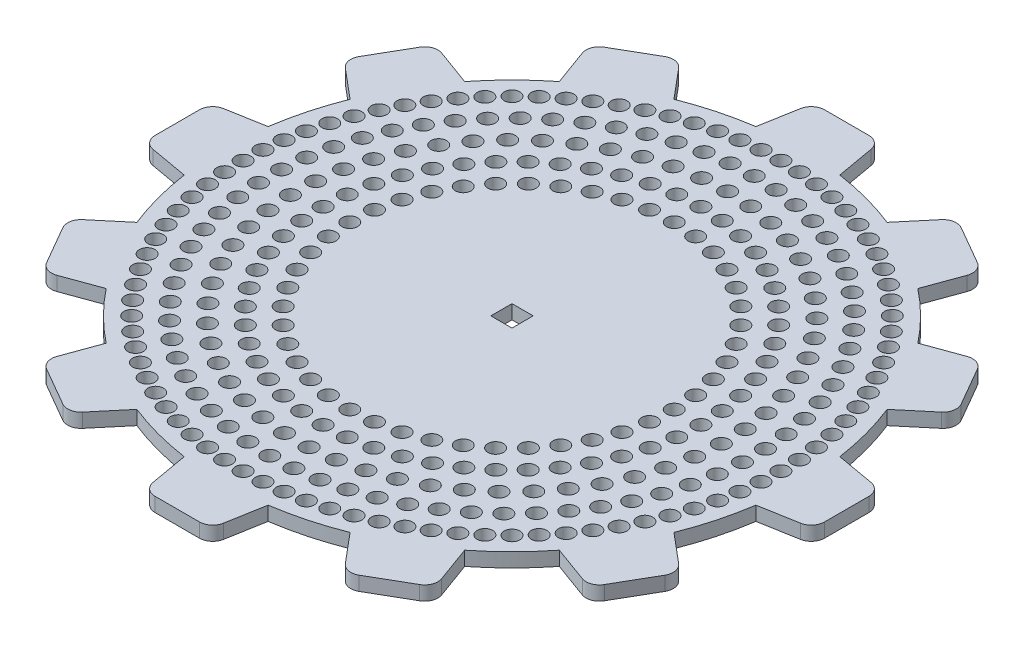
SolidWorks part; units mm, degrees
material "Balsa"
ref_plane "Front Plane" through (0, 0, 0) normal (0, 0, 1) x (1, 0, 0)
ref_plane "Top Plane" through (0, 0, 0) normal (0, 1, 0) x (1, 0, 0)
ref_plane "Right Plane" through (0, 0, 0) normal (1, 0, 0) x (0, 0, -1)
sketch "Sketch1" plane through (0, 0, 0) normal (0, 1, 0) x (1, 0, 0)
  line L0 (0, 109) -> (0, 121) construction
  line L1 (-4.7625, 4.7625) -> (4.7625, 4.7625)
  line L2 (-4.7625, 4.7625) -> (-4.7625, -4.7625)
  line L7 (-4.7625, -4.7625) -> (4.7625, -4.7625)
  line L8 (0, 109) -> (0, 97) construction
  line L9 (0, 97) -> (0, 85) construction
  line L10 (0, 85) -> (0, 73) construction
  line L11 (4.7625, 4.7625) -> (4.7625, -4.7625)
  line L12 (-4.7625, 4.7625) -> (4.7625, -4.7625) construction
  line L13 (-4.7625, -4.7625) -> (4.7625, 4.7625) construction
  circle A0 centre (0, 0) radius 130
  circle A39 centre (0, 73) radius 3.5
  circle A40 centre (0, 85) radius 3.5
  circle A41 centre (0, 97) radius 3.5
  circle A42 centre (0, 109) radius 3.5
  circle A43 centre (10.3611, 108.5064) radius 3.5
  circle A44 centre (20.6284, 107.0302) radius 3.5
  circle A45 centre (30.7088, 104.5847) radius 3.5
  circle A46 centre (40.5112, 101.1921) radius 3.5
  circle A47 centre (49.9467, 96.8831) radius 3.5
  circle A48 centre (58.9298, 91.6966) radius 3.5
  circle A49 centre (67.3793, 85.6798) radius 3.5
  circle A50 centre (75.2186, 78.887) radius 3.5
  circle A51 centre (82.3767, 71.3798) radius 3.5
  circle A52 centre (88.7888, 63.2262) radius 3.5
  circle A53 centre (94.3968, 54.5) radius 3.5
  circle A54 centre (99.1499, 45.2802) radius 3.5
  circle A55 centre (103.0051, 35.6504) radius 3.5
  circle A56 centre (105.9275, 25.6977) radius 3.5
  circle A57 centre (107.8905, 15.5123) radius 3.5
  circle A58 centre (108.8765, 5.1864) radius 3.5
  circle A59 centre (108.8765, -5.1864) radius 3.5
  circle A60 centre (107.8905, -15.5123) radius 3.5
  circle A61 centre (105.9275, -25.6977) radius 3.5
  circle A62 centre (103.0051, -35.6504) radius 3.5
  circle A63 centre (99.1499, -45.2802) radius 3.5
  circle A64 centre (94.3968, -54.5) radius 3.5
  circle A65 centre (88.7888, -63.2262) radius 3.5
  circle A66 centre (82.3767, -71.3798) radius 3.5
  circle A67 centre (75.2186, -78.887) radius 3.5
  circle A68 centre (67.3793, -85.6798) radius 3.5
  circle A69 centre (58.9298, -91.6966) radius 3.5
  circle A70 centre (49.9467, -96.8831) radius 3.5
  circle A71 centre (40.5112, -101.1921) radius 3.5
  circle A72 centre (30.7088, -104.5847) radius 3.5
  circle A73 centre (20.6284, -107.0302) radius 3.5
  circle A74 centre (10.3611, -108.5064) radius 3.5
  circle A75 centre (0, -109) radius 3.5
  circle A76 centre (-10.3611, -108.5064) radius 3.5
  circle A77 centre (-20.6284, -107.0302) radius 3.5
  circle A78 centre (-30.7088, -104.5847) radius 3.5
  circle A79 centre (-40.5112, -101.1921) radius 3.5
  circle A80 centre (-49.9467, -96.8831) radius 3.5
  circle A81 centre (-58.9298, -91.6966) radius 3.5
  circle A82 centre (-67.3793, -85.6798) radius 3.5
  circle A83 centre (-75.2186, -78.887) radius 3.5
  circle A84 centre (-82.3767, -71.3798) radius 3.5
  circle A85 centre (-88.7888, -63.2262) radius 3.5
  circle A86 centre (-94.3968, -54.5) radius 3.5
  circle A87 centre (-99.1499, -45.2802) radius 3.5
  circle A88 centre (-103.0051, -35.6504) radius 3.5
  circle A89 centre (-105.9275, -25.6977) radius 3.5
  circle A90 centre (-107.8905, -15.5123) radius 3.5
  circle A91 centre (-108.8765, -5.1864) radius 3.5
  circle A92 centre (-108.8765, 5.1864) radius 3.5
  circle A93 centre (-107.8905, 15.5123) radius 3.5
  circle A94 centre (-105.9275, 25.6977) radius 3.5
  circle A95 centre (-103.0051, 35.6504) radius 3.5
  circle A96 centre (-99.1499, 45.2802) radius 3.5
  circle A97 centre (-94.3968, 54.5) radius 3.5
  circle A98 centre (-88.7888, 63.2262) radius 3.5
  circle A99 centre (-82.3767, 71.3798) radius 3.5
  circle A100 centre (-75.2186, 78.887) radius 3.5
  circle A101 centre (-67.3793, 85.6798) radius 3.5
  circle A102 centre (-58.9298, 91.6966) radius 3.5
  circle A103 centre (-49.9467, 96.8831) radius 3.5
  circle A104 centre (-40.5112, 101.1921) radius 3.5
  circle A105 centre (-30.7088, 104.5847) radius 3.5
  circle A106 centre (-20.6284, 107.0302) radius 3.5
  circle A107 centre (-10.3611, 108.5064) radius 3.5
  circle A108 centre (11.0572, 96.3677) radius 3.5
  circle A109 centre (21.9702, 94.4792) radius 3.5
  circle A110 centre (32.5968, 91.3589) radius 3.5
  circle A111 centre (42.7984, 87.0476) radius 3.5
  circle A112 centre (52.4422, 81.6016) radius 3.5
  circle A113 centre (61.4022, 75.0917) radius 3.5
  circle A114 centre (69.5618, 67.6029) radius 3.5
  circle A115 centre (76.8145, 59.2328) radius 3.5
  circle A116 centre (83.0659, 50.0906) radius 3.5
  circle A117 centre (88.2343, 40.2953) radius 3.5
  circle A118 centre (92.2525, 29.9746) radius 3.5
  circle A119 centre (95.068, 19.2633) radius 3.5
  circle A120 centre (96.6442, 8.3008) radius 3.5
  circle A121 centre (96.9604, -2.7699) radius 3.5
  circle A122 centre (96.0127, -13.8045) radius 3.5
  circle A123 centre (93.8132, -24.6592) radius 3.5
  circle A124 centre (90.3908, -35.1923) radius 3.5
  circle A125 centre (85.79, -45.2667) radius 3.5
  circle A126 centre (80.0708, -54.751) radius 3.5
  circle A127 centre (73.3077, -63.5215) radius 3.5
  circle A128 centre (65.589, -71.4639) radius 3.5
  circle A129 centre (57.0152, -78.4746) radius 3.5
  circle A130 centre (47.6981, -84.4624) radius 3.5
  circle A131 centre (37.7592, -89.349) radius 3.5
  circle A132 centre (27.3281, -93.0708) radius 3.5
  circle A133 centre (16.5407, -95.5793) radius 3.5
  circle A134 centre (5.5376, -96.8418) radius 3.5
  circle A135 centre (-5.5376, -96.8418) radius 3.5
  circle A136 centre (-16.5407, -95.5793) radius 3.5
  circle A137 centre (-27.3281, -93.0708) radius 3.5
  circle A138 centre (-37.7592, -89.349) radius 3.5
  circle A139 centre (-47.6981, -84.4624) radius 3.5
  circle A140 centre (-57.0152, -78.4746) radius 3.5
  circle A141 centre (-65.589, -71.4639) radius 3.5
  circle A142 centre (-73.3077, -63.5215) radius 3.5
  circle A143 centre (-80.0708, -54.751) radius 3.5
  circle A144 centre (-85.79, -45.2667) radius 3.5
  circle A145 centre (-90.3908, -35.1923) radius 3.5
  circle A146 centre (-93.8132, -24.6592) radius 3.5
  circle A147 centre (-96.0127, -13.8045) radius 3.5
  circle A148 centre (-96.9604, -2.7699) radius 3.5
  circle A149 centre (-96.6442, 8.3008) radius 3.5
  circle A150 centre (-95.068, 19.2633) radius 3.5
  circle A151 centre (-92.2525, 29.9746) radius 3.5
  circle A152 centre (-88.2343, 40.2953) radius 3.5
  circle A153 centre (-83.0659, 50.0906) radius 3.5
  circle A154 centre (-76.8145, 59.2328) radius 3.5
  circle A155 centre (-69.5618, 67.6029) radius 3.5
  circle A156 centre (-61.4022, 75.0917) radius 3.5
  circle A157 centre (-52.4422, 81.6016) radius 3.5
  circle A158 centre (-42.7984, 87.0476) radius 3.5
  circle A159 centre (-32.5968, 91.3589) radius 3.5
  circle A160 centre (-21.9702, 94.4792) radius 3.5
  circle A161 centre (-11.0572, 96.3677) radius 3.5
  circle A162 centre (10.2456, 84.3803) radius 3.5
  circle A163 centre (20.3418, 82.5301) radius 3.5
  circle A164 centre (30.1414, 79.4764) radius 3.5
  circle A165 centre (39.5015, 75.2638) radius 3.5
  circle A166 centre (48.2855, 69.9536) radius 3.5
  circle A167 centre (56.3654, 63.6234) radius 3.5
  circle A168 centre (63.6234, 56.3654) radius 3.5
  circle A169 centre (69.9536, 48.2855) radius 3.5
  circle A170 centre (75.2638, 39.5015) radius 3.5
  circle A171 centre (79.4764, 30.1414) radius 3.5
  circle A172 centre (82.5301, 20.3418) radius 3.5
  circle A173 centre (84.3803, 10.2456) radius 3.5
  circle A174 centre (85, 0) radius 3.5
  circle A175 centre (84.3803, -10.2456) radius 3.5
  circle A176 centre (82.5301, -20.3418) radius 3.5
  circle A177 centre (79.4764, -30.1414) radius 3.5
  circle A178 centre (75.2638, -39.5015) radius 3.5
  circle A179 centre (69.9536, -48.2855) radius 3.5
  circle A180 centre (63.6234, -56.3654) radius 3.5
  circle A181 centre (56.3654, -63.6234) radius 3.5
  circle A182 centre (48.2855, -69.9536) radius 3.5
  circle A183 centre (39.5015, -75.2638) radius 3.5
  circle A184 centre (30.1414, -79.4764) radius 3.5
  circle A185 centre (20.3418, -82.5301) radius 3.5
  circle A186 centre (10.2456, -84.3803) radius 3.5
  circle A187 centre (0, -85) radius 3.5
  circle A188 centre (-10.2456, -84.3803) radius 3.5
  circle A189 centre (-20.3418, -82.5301) radius 3.5
  circle A190 centre (-30.1414, -79.4764) radius 3.5
  circle A191 centre (-39.5015, -75.2638) radius 3.5
  circle A192 centre (-48.2855, -69.9536) radius 3.5
  circle A193 centre (-56.3654, -63.6234) radius 3.5
  circle A194 centre (-63.6234, -56.3654) radius 3.5
  circle A195 centre (-69.9536, -48.2855) radius 3.5
  circle A196 centre (-75.2638, -39.5015) radius 3.5
  circle A197 centre (-79.4764, -30.1414) radius 3.5
  circle A198 centre (-82.5301, -20.3418) radius 3.5
  circle A199 centre (-84.3803, -10.2456) radius 3.5
  circle A200 centre (-85, 0) radius 3.5
  circle A201 centre (-84.3803, 10.2456) radius 3.5
  circle A202 centre (-82.5301, 20.3418) radius 3.5
  circle A203 centre (-79.4764, 30.1414) radius 3.5
  circle A204 centre (-75.2638, 39.5015) radius 3.5
  circle A205 centre (-69.9536, 48.2855) radius 3.5
  circle A206 centre (-63.6234, 56.3654) radius 3.5
  circle A207 centre (-56.3654, 63.6234) radius 3.5
  circle A208 centre (-48.2855, 69.9536) radius 3.5
  circle A209 centre (-39.5015, 75.2638) radius 3.5
  circle A210 centre (-30.1414, 79.4764) radius 3.5
  circle A211 centre (-20.3418, 82.5301) radius 3.5
  circle A212 centre (-10.2456, 84.3803) radius 3.5
  circle A214 centre (10.389, 72.257) radius 3.5
  circle A215 centre (20.5665, 70.043) radius 3.5
  circle A216 centre (30.3253, 66.4031) radius 3.5
  circle A217 centre (39.4668, 61.4115) radius 3.5
  circle A218 centre (47.8048, 55.1697) radius 3.5
  circle A219 centre (55.1697, 47.8048) radius 3.5
  circle A220 centre (61.4115, 39.4668) radius 3.5
  circle A221 centre (66.4031, 30.3253) radius 3.5
  circle A222 centre (70.043, 20.5665) radius 3.5
  circle A223 centre (72.257, 10.389) radius 3.5
  circle A224 centre (73, 0) radius 3.5
  circle A225 centre (72.257, -10.389) radius 3.5
  circle A226 centre (70.043, -20.5665) radius 3.5
  circle A227 centre (66.4031, -30.3253) radius 3.5
  circle A228 centre (61.4115, -39.4668) radius 3.5
  circle A229 centre (55.1697, -47.8048) radius 3.5
  circle A230 centre (47.8048, -55.1697) radius 3.5
  circle A231 centre (39.4668, -61.4115) radius 3.5
  circle A232 centre (30.3253, -66.4031) radius 3.5
  circle A233 centre (20.5665, -70.043) radius 3.5
  circle A234 centre (10.389, -72.257) radius 3.5
  circle A235 centre (0, -73) radius 3.5
  circle A236 centre (-10.389, -72.257) radius 3.5
  circle A237 centre (-20.5665, -70.043) radius 3.5
  circle A238 centre (-30.3253, -66.4031) radius 3.5
  circle A239 centre (-39.4668, -61.4115) radius 3.5
  circle A240 centre (-47.8048, -55.1697) radius 3.5
  circle A241 centre (-55.1697, -47.8048) radius 3.5
  circle A242 centre (-61.4115, -39.4668) radius 3.5
  circle A243 centre (-66.4031, -30.3253) radius 3.5
  circle A244 centre (-70.043, -20.5665) radius 3.5
  circle A245 centre (-72.257, -10.389) radius 3.5
  circle A246 centre (-73, 0) radius 3.5
  circle A247 centre (-72.257, 10.389) radius 3.5
  circle A248 centre (-70.043, 20.5665) radius 3.5
  circle A249 centre (-66.4031, 30.3253) radius 3.5
  circle A250 centre (-61.4115, 39.4668) radius 3.5
  circle A251 centre (-55.1697, 47.8048) radius 3.5
  circle A252 centre (-47.8048, 55.1697) radius 3.5
  circle A253 centre (-39.4668, 61.4115) radius 3.5
  circle A254 centre (-30.3253, 66.4031) radius 3.5
  circle A255 centre (-20.5665, 70.043) radius 3.5
  circle A256 centre (-10.389, 72.257) radius 3.5
  circle A258 centre (0, 121) radius 3.5
  circle A259 centre (8.632, 120.6917) radius 3.5
  circle A260 centre (17.2201, 119.7684) radius 3.5
  circle A261 centre (25.7204, 118.2348) radius 3.5
  circle A262 centre (34.0896, 116.0986) radius 3.5
  circle A263 centre (42.2852, 113.3709) radius 3.5
  circle A264 centre (50.2652, 110.0655) radius 3.5
  circle A265 centre (57.9891, 106.1992) radius 3.5
  circle A266 centre (65.4175, 101.7917) radius 3.5
  circle A267 centre (72.5126, 96.8655) radius 3.5
  circle A268 centre (79.2381, 91.4457) radius 3.5
  circle A269 centre (85.5599, 85.5599) radius 3.5
  circle A270 centre (91.4457, 79.2381) radius 3.5
  circle A271 centre (96.8655, 72.5126) radius 3.5
  circle A272 centre (101.7917, 65.4175) radius 3.5
  circle A273 centre (106.1992, 57.9891) radius 3.5
  circle A274 centre (110.0655, 50.2652) radius 3.5
  circle A275 centre (113.3709, 42.2852) radius 3.5
  circle A276 centre (116.0986, 34.0896) radius 3.5
  circle A277 centre (118.2348, 25.7204) radius 3.5
  circle A278 centre (119.7684, 17.2201) radius 3.5
  circle A279 centre (120.6917, 8.632) radius 3.5
  circle A280 centre (121, 0) radius 3.5
  circle A281 centre (120.6917, -8.632) radius 3.5
  circle A282 centre (119.7684, -17.2201) radius 3.5
  circle A283 centre (118.2348, -25.7204) radius 3.5
  circle A284 centre (116.0986, -34.0896) radius 3.5
  circle A285 centre (113.3709, -42.2852) radius 3.5
  circle A286 centre (110.0655, -50.2652) radius 3.5
  circle A287 centre (106.1992, -57.9891) radius 3.5
  circle A288 centre (101.7917, -65.4175) radius 3.5
  circle A289 centre (96.8655, -72.5126) radius 3.5
  circle A290 centre (91.4457, -79.2381) radius 3.5
  circle A291 centre (85.5599, -85.5599) radius 3.5
  circle A292 centre (79.2381, -91.4457) radius 3.5
  circle A293 centre (72.5126, -96.8655) radius 3.5
  circle A294 centre (65.4175, -101.7917) radius 3.5
  circle A295 centre (57.9891, -106.1992) radius 3.5
  circle A296 centre (50.2652, -110.0655) radius 3.5
  circle A297 centre (42.2852, -113.3709) radius 3.5
  circle A298 centre (34.0896, -116.0986) radius 3.5
  circle A299 centre (25.7204, -118.2348) radius 3.5
  circle A300 centre (17.2201, -119.7684) radius 3.5
  circle A301 centre (8.632, -120.6917) radius 3.5
  circle A302 centre (0, -121) radius 3.5
  circle A303 centre (-8.632, -120.6917) radius 3.5
  circle A304 centre (-17.2201, -119.7684) radius 3.5
  circle A305 centre (-25.7204, -118.2348) radius 3.5
  circle A306 centre (-34.0896, -116.0986) radius 3.5
  circle A307 centre (-42.2852, -113.3709) radius 3.5
  circle A308 centre (-50.2652, -110.0655) radius 3.5
  circle A309 centre (-57.9891, -106.1992) radius 3.5
  circle A310 centre (-65.4175, -101.7917) radius 3.5
  circle A311 centre (-72.5126, -96.8655) radius 3.5
  circle A312 centre (-79.2381, -91.4457) radius 3.5
  circle A313 centre (-85.5599, -85.5599) radius 3.5
  circle A314 centre (-91.4457, -79.2381) radius 3.5
  circle A315 centre (-96.8655, -72.5126) radius 3.5
  circle A316 centre (-101.7917, -65.4175) radius 3.5
  circle A317 centre (-106.1992, -57.9891) radius 3.5
  circle A318 centre (-110.0655, -50.2652) radius 3.5
  circle A319 centre (-113.3709, -42.2852) radius 3.5
  circle A320 centre (-116.0986, -34.0896) radius 3.5
  circle A321 centre (-118.2348, -25.7204) radius 3.5
  circle A322 centre (-119.7684, -17.2201) radius 3.5
  circle A323 centre (-120.6917, -8.632) radius 3.5
  circle A324 centre (-121, 0) radius 3.5
  circle A325 centre (-120.6917, 8.632) radius 3.5
  circle A326 centre (-119.7684, 17.2201) radius 3.5
  circle A327 centre (-118.2348, 25.7204) radius 3.5
  circle A328 centre (-116.0986, 34.0896) radius 3.5
  circle A329 centre (-113.3709, 42.2852) radius 3.5
  circle A330 centre (-110.0655, 50.2652) radius 3.5
  circle A331 centre (-106.1992, 57.9891) radius 3.5
  circle A332 centre (-101.7917, 65.4175) radius 3.5
  circle A333 centre (-96.8655, 72.5126) radius 3.5
  circle A334 centre (-91.4457, 79.2381) radius 3.5
  circle A335 centre (-85.5599, 85.5599) radius 3.5
  circle A336 centre (-79.2381, 91.4457) radius 3.5
  circle A337 centre (-72.5126, 96.8655) radius 3.5
  circle A338 centre (-65.4175, 101.7917) radius 3.5
  circle A339 centre (-57.9891, 106.1992) radius 3.5
  circle A340 centre (-50.2652, 110.0655) radius 3.5
  circle A341 centre (-42.2852, 113.3709) radius 3.5
  circle A342 centre (-34.0896, 116.0986) radius 3.5
  circle A343 centre (-25.7204, 118.2348) radius 3.5
  circle A344 centre (-17.2201, 119.7684) radius 3.5
  circle A345 centre (-8.632, 120.6917) radius 3.5
  point P619 (0, 0)
  dimension "D2" = 12
  dimension "D3" = 260
  dimension "D4" = 73
  dimension "D12" = 7
  dimension "D5" = 9.525
  dimension "D8" = 66
  dimension "D9" = 55
  dimension "D10" = 52
  dimension "D11" = 44
  dimension "D6" = 88
extrude "Boss-Extrude1" add sketch "Sketch1" along normal blind 6.35
sketch "Sketch2" plane through (0, 6.35, 0) normal (0, 1, 0) x (1, 0, 0)
  line L0 (0, 0) -> (0, 202.4314) construction
  line L1 (0, 0) -> (-221.3243, 0) construction
  line L2 (0, 0) -> (223.2936, 0) construction
  line L3 (0, 150.6218) -> (15, 150.6218)
  line L4 (0, 150.6218) -> (-15, 150.6218)
  line L5 (-15, 150.6218) -> (-18.8792, 128.6218)
  line L6 (15, 150.6218) -> (18.8792, 128.6218)
  line L7 (62.3205, 137.9423) -> (47.9611, 120.8294)
  line L8 (75.3109, 130.4423) -> (88.3013, 122.9423)
  line L9 (75.3109, 130.4423) -> (62.3205, 137.9423)
  line L10 (88.3013, 122.9423) -> (80.6608, 101.9502)
  line L11 (122.9423, 88.3013) -> (101.9502, 80.6608)
  line L12 (130.4423, 75.3109) -> (137.9423, 62.3205)
  line L13 (130.4423, 75.3109) -> (122.9423, 88.3013)
  line L14 (137.9423, 62.3205) -> (120.8294, 47.9611)
  line L15 (150.6218, 15) -> (128.6218, 18.8792)
  line L16 (150.6218, 0) -> (150.6218, -15)
  line L17 (150.6218, 0) -> (150.6218, 15)
  line L18 (150.6218, -15) -> (128.6218, -18.8792)
  line L19 (137.9423, -62.3205) -> (120.8294, -47.9611)
  line L20 (130.4423, -75.3109) -> (122.9423, -88.3013)
  line L21 (130.4423, -75.3109) -> (137.9423, -62.3205)
  line L22 (122.9423, -88.3013) -> (101.9502, -80.6608)
  line L23 (88.3013, -122.9423) -> (80.6608, -101.9502)
  line L24 (75.3109, -130.4423) -> (62.3205, -137.9423)
  line L25 (75.3109, -130.4423) -> (88.3013, -122.9423)
  line L26 (62.3205, -137.9423) -> (47.9611, -120.8294)
  line L27 (15, -150.6218) -> (18.8792, -128.6218)
  line L28 (0, -150.6218) -> (-15, -150.6218)
  line L29 (0, -150.6218) -> (15, -150.6218)
  line L30 (-15, -150.6218) -> (-18.8792, -128.6218)
  line L31 (-62.3205, -137.9423) -> (-47.9611, -120.8294)
  line L32 (-75.3109, -130.4423) -> (-88.3013, -122.9423)
  line L33 (-75.3109, -130.4423) -> (-62.3205, -137.9423)
  line L34 (-88.3013, -122.9423) -> (-80.6608, -101.9502)
  line L35 (-122.9423, -88.3013) -> (-101.9502, -80.6608)
  line L36 (-130.4423, -75.3109) -> (-137.9423, -62.3205)
  line L37 (-130.4423, -75.3109) -> (-122.9423, -88.3013)
  line L38 (-137.9423, -62.3205) -> (-120.8294, -47.9611)
  line L39 (-150.6218, -15) -> (-128.6218, -18.8792)
  line L40 (-150.6218, 0) -> (-150.6218, 15)
  line L41 (-150.6218, 0) -> (-150.6218, -15)
  line L42 (-150.6218, 15) -> (-128.6218, 18.8792)
  line L43 (-137.9423, 62.3205) -> (-120.8294, 47.9611)
  line L44 (-130.4423, 75.3109) -> (-122.9423, 88.3013)
  line L45 (-130.4423, 75.3109) -> (-137.9423, 62.3205)
  line L46 (-122.9423, 88.3013) -> (-101.9502, 80.6608)
  line L47 (-88.3013, 122.9423) -> (-80.6608, 101.9502)
  line L48 (-75.3109, 130.4423) -> (-62.3205, 137.9423)
  line L49 (-75.3109, 130.4423) -> (-88.3013, 122.9423)
  line L50 (-62.3205, 137.9423) -> (-47.9611, 120.8294)
  arc A0 (18.8792, 128.6218) -> (-18.8792, 128.6218) centre (0, 0) ccw
  circle A1 centre (0, 0) radius 130 construction
  arc A2 (80.6608, 101.9502) -> (47.9611, 120.8294) centre (0, 0) ccw
  arc A3 (120.8294, 47.9611) -> (101.9502, 80.6608) centre (0, 0) ccw
  arc A4 (128.6218, -18.8792) -> (128.6218, 18.8792) centre (0, 0) ccw
  arc A5 (101.9502, -80.6608) -> (120.8294, -47.9611) centre (0, 0) ccw
  arc A6 (47.9611, -120.8294) -> (80.6608, -101.9502) centre (0, 0) ccw
  arc A7 (-18.8792, -128.6218) -> (18.8792, -128.6218) centre (0, 0) ccw
  arc A8 (-80.6608, -101.9502) -> (-47.9611, -120.8294) centre (0, 0) ccw
  arc A9 (-120.8294, -47.9611) -> (-101.9502, -80.6608) centre (0, 0) ccw
  arc A10 (-128.6218, 18.8792) -> (-128.6218, -18.8792) centre (0, 0) ccw
  arc A11 (-101.9502, 80.6608) -> (-120.8294, 47.9611) centre (0, 0) ccw
  arc A12 (-47.9611, 120.8294) -> (-80.6608, 101.9502) centre (0, 0) ccw
  point P70 (0, 0)
  dimension "D1" = 100
  dimension "D2" = 100
  dimension "D3" = 15
  dimension "D4" = 22
  dimension "D5" = 12
extrude "Boss-Extrude2" add sketch "Sketch2" against normal up to surface (6.35 mm away) up to face at (0, 0, -117.5)
fillet "Fillet3" radius 6 23 edges at (88.3013, 3.175, -122.9423) (62.3205, 3.175, -137.9423) (137.9423, 3.175, -62.3205) (150.6218, 3.175, -15) (150.6218, 3.175, 15) (137.9423, 3.175, 62.3205) (122.9423, 3.175, 88.3013) (88.3013, 3.175, 122.9423) (62.3205, 3.175, 137.9423) (15, 3.175, 150.6218) (-15, 3.175, 150.6218) (-62.3205, 3.175, 137.9423) (-88.3013, 3.175, 122.9423) (-122.9423, 3.175, 88.3013) (-137.9423, 3.175, 62.3205) (-150.6218, 3.175, 15) (15, 3.175, -150.6218) (-15, 3.175, -150.6218) (-62.3205, 3.175, -137.9423) (-88.3013, 3.175, -122.9423) (-122.9423, 3.175, -88.3013) (-137.9423, 3.175, -62.3205) (-150.6218, 3.175, -15)
fillet "Fillet4" radius 6 1 edges at (122.9423, 3.175, -88.3013)
sketch "Sketch3" plane through (0, 6.35, 0) normal (0, 1, 0) x (1, 0, 0)
  circle A0 centre (0, 0) radius 50 construction
  circle A1 centre (0, 0) radius 37.5 construction
  text T0 "PARTHENOPE  |  WPI MUSICAL ROBOTICS A18  |  MATTHEW BISSON, JORDAN GROTZ, CESAR GUERRERO, MICHAEL SIDLER  |  "
  text T1 "DISK 1  |  10RPS  |  A4 (44 holes)  |  C5 (52 holes)  |  C#5 (55 holes)  |  E5 (66 holes)  |  A5 (88 holes)  |  "
  dimension "D1" = 100
  dimension "D2" = 75
